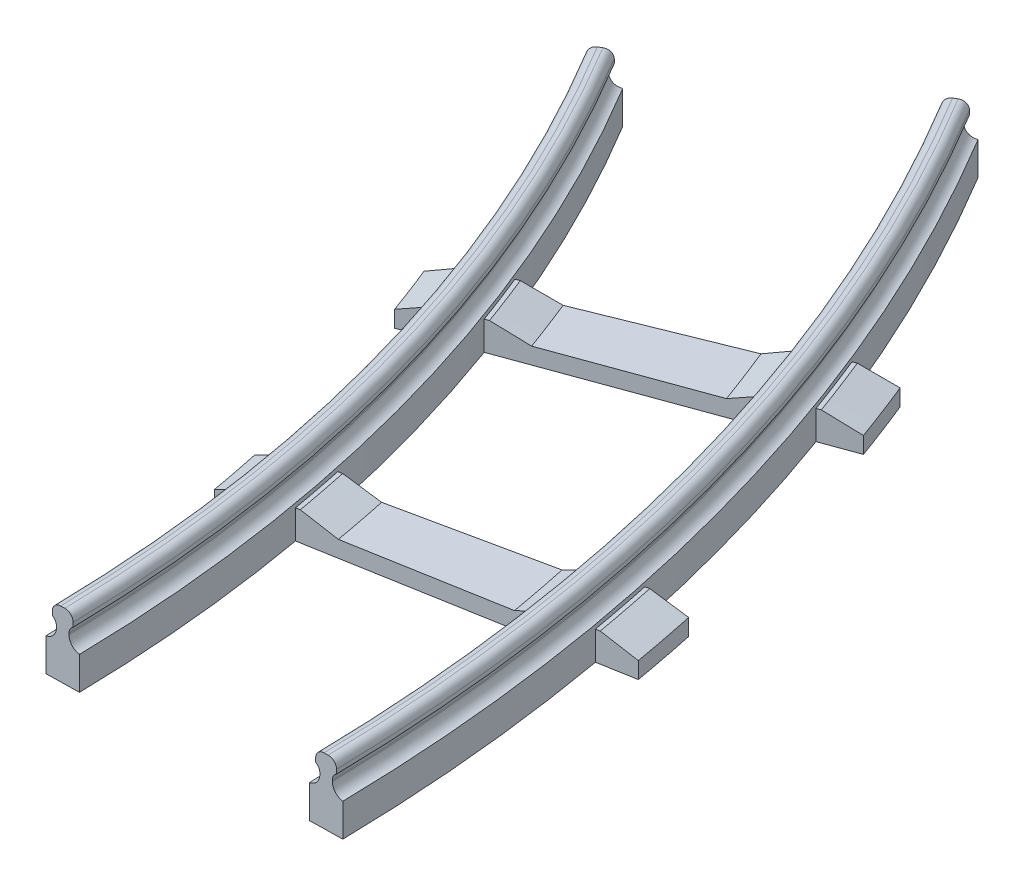
SolidWorks part; units mm, degrees
other "标注1"
sketch "草图3" plane through (-22.25, 4, -10) normal (-0.231, 0.6469, -0.7268) x (-0.9696, -0.2151, 0.1167)
other "标注2"
sketch "草图4" plane through (22.25, 8, -30) normal (0.0083, 0.0567, -0.9984) x (-0.9991, 0.0415, -0.0059)
ref_plane "前视基准面" through (0, 0, 0) normal (0, 0, 1) x (1, 0, 0)
ref_plane "上视基准面" through (0, 0, 0) normal (0, 1, 0) x (1, 0, 0)
ref_plane "右视基准面" through (0, 0, 0) normal (1, 0, 0) x (0, 0, -1)
other "Configuration Table"
sketch "草图1" plane through (0, 0, 0) normal (0, 1, 0) x (1, 0, 0)
  line L0 (-13.75, 14.5) -> (-13.75, -14.5)
  line L13 (-17.75, -14.5) -> (17.75, -14.5)
  line L21 (-17.75, -14.5) -> (-17.75, 14.5)
  line L22 (-17.75, 14.5) -> (17.75, 14.5)
  line L23 (17.75, -14.5) -> (17.75, 14.5)
  line L24 (-17.75, -14.5) -> (17.75, 14.5) construction
  line L25 (-17.75, 14.5) -> (17.75, -14.5) construction
  line L27 (13.75, 14.5) -> (13.75, -14.5)
  line L29 (-13.75, 0) -> (13.75, 0) construction
  line L32 (-22.25, 14.5) -> (22.25, 14.5)
  line L33 (-22.25, 14.5) -> (-22.25, 6.5)
  line L34 (-22.25, 6.5) -> (22.25, 6.5)
  line L35 (22.25, 14.5) -> (22.25, 6.5)
  point P0 (0, 0)
  point P15 (0, 6.5)
  dimension "D3" = 27.5
  dimension "D4" = 8
  dimension "D1" = 35.5
  dimension "D2" = 29
  dimension "D5" = 44.5
extrude "凸台-拉伸1" add sketch "草图1" along normal blind 4 contours L34 L21 L13 L0 | L34 L27 L13 L23 | L27 L34 L23 L22 | L21 L34 L0 L22 region at (-15.75, 0, -10.5) region at (-15.75, 0, 4) region at (15.75, 0, -10.5) region at (15.75, 0, 4)
extrude "凸台-拉伸2" add sketch "草图1<7>" along normal blind 3.5 contours L34 L35 L32 L33
sketch "草图1<7>" plane through (0, 0, 0) normal (0, 1, 0) x (1, 0, 0) same geometry as "草图1"
sketch "草图2" plane through (0, 0, -14.5) normal (0, 0, -1) x (-1, 0, 0)
  line L0 (18.25, 3.5) -> (22.25, 2)
  line L1 (22.25, 3.5) -> (18.25, 3.5)
  line L2 (22.25, 3.5) -> (22.25, 2)
  line L3 (22.25, 2) -> (18.25, 2) construction
  line L4 (18.25, 3.5) -> (18.25, 2) construction
  line L5 (-22.25, 2) -> (-18.25, 3.5)
  line L6 (-22.25, 3.5) -> (-18.25, 3.5)
  line L7 (-22.25, 3.5) -> (-22.25, 2)
  line L8 (-22.25, 2) -> (-18.25, 2) construction
  line L9 (-18.25, 3.5) -> (-18.25, 2) construction
  line L10 (13.75, 3.5) -> (-13.75, 3.5) construction
  line L11 (-13.25, 3.5) -> (-9.25, 3.5)
  line L12 (-13.25, 3.5) -> (-13.25, 2) construction
  line L13 (-13.25, 2) -> (-9.25, 2) construction
  line L14 (-9.25, 3.5) -> (-9.25, 2)
  line L15 (-13.75, 3.5) -> (-13.25, 3.5) construction
  line L16 (13.25, 3.5) -> (9.25, 3.5)
  line L17 (13.25, 3.5) -> (13.25, 2) construction
  line L18 (13.25, 2) -> (9.25, 2) construction
  line L19 (9.25, 3.5) -> (9.25, 2)
  line L20 (13.25, 3.5) -> (13.75, 3.5) construction
  line L21 (17.75, 3.5) -> (18.25, 3.5) construction
  line L22 (-13.25, 3.5) -> (-9.25, 2)
  line L23 (9.25, 2) -> (13.25, 3.5)
  line L24 (-9.25, 2) -> (9.25, 2)
  line L25 (-9.25, 3.5) -> (9.25, 3.5)
  line L26 (-15.75, 4) -> (-15.75, 6.5) construction
  line L27 (14.5, 8) -> (17, 8)
  line L28 (14.5, 8) -> (14.5, 6.5)
  line L29 (14.5, 6.5) -> (17, 6.5)
  line L30 (17, 8) -> (17, 6.5)
  line L31 (-17, 8) -> (-14.5, 8)
  line L32 (-17, 8) -> (-17, 6.5)
  line L33 (-17, 6.5) -> (-14.5, 6.5)
  line L34 (-14.5, 8) -> (-14.5, 6.5)
  line L35 (-13.75, 4) -> (-17.75, 4) construction
  line L36 (15.75, 6.5) -> (15.75, 4) construction
  line L37 (17.75, 4) -> (13.75, 4) construction
  line L38 (15, 6.5) -> (15, 4)
  line L39 (16.5, 6.5) -> (16.5, 4)
  line L40 (16.5, 4) -> (15.75, 4)
  line L41 (15.75, 4) -> (15, 4)
  line L42 (-16.5, 6.5) -> (-16.5, 4)
  line L43 (-16.5, 4) -> (-15.75, 4)
  line L44 (-15.75, 4) -> (-15, 4)
  line L45 (-15, 4) -> (-15, 6.5)
  line M9 (22.25, 3.5) -> (17.75, 3.5)
  line M11 (17.75, 4) -> (13.75, 4)
  line M13 (13.75, 3.5) -> (-13.75, 3.5)
  line M15 (-13.75, 4) -> (-17.75, 4)
  line M17 (-17.75, 3.5) -> (-22.25, 3.5)
  line M18 (-22.25, 3.5) -> (-22.25, 0)
  line M20 (22.25, 0) -> (22.25, 3.5)
  dimension "D1" = 4
  dimension "D2" = 1.5
  dimension "D3" = 2.5
  dimension "D4" = 1.5
  dimension "D5" = 2.5
  dimension "D6" = 1.5
extrude "切除-拉伸1" cut sketch "草图2" against normal through all contours L14 L24 L19 M13 | L19 L23 M13 | L22 L14 M13 | L5 M18 M17 | L0 M9 M20 region at (-20.9167, 3, -14.5) region at (20.9167, 3, -14.5) region at (10.5833, 3, -14.5) region at (0, 2.75, -14.5) region at (-10.5833, 3, -14.5)
extrude "凸台-拉伸4" add sketch "草图2<3>" against normal through all contours L34 L31 L32 L33 | L45 L33 L42 M15 | L30 L27 L28 L29 | L39 L29 L38 M11 region at (-15.75, 7.25, -14.5) region at (-15.75, 5.25, -14.5) region at (15.75, 7.25, -14.5) region at (15.75, 5.25, -14.5)
sketch "草图2<3>" plane through (0, 0, -14.5) normal (0, 0, -1) x (-1, 0, 0) same geometry as "草图2"
fillet "圆角1" radius 1 4 edges at (-16.5, 6.5, 0) (-15, 6.5, 0) (15, 6.5, 0) (16.5, 6.5, 0)
fillet "圆角2" radius 1.5 4 edges at (16.5, 4, 0) (15, 4, 0) (-15, 4, 0) (-16.5, 4, 0)
fillet "圆角3" radius 1 4 edges at (-17, 8, 0) (14.5, 8, 0) (17, 8, 0) (-14.5, 8, 0)
sketch "草图5" plane through (0, 0, -14.5) normal (0, 0, -1) x (-1, 0, 0)
  line L26 (17, 6.5) -> (17, 7)
  line L27 (16, 8) -> (15.5, 8)
  line L28 (14.5, 7) -> (14.5, 6.5)
  line L29 (15, 5.634) -> (15, 5.479)
  line L30 (13.75, 4) -> (13.75, 3.5)
  line L31 (13.75, 3.5) -> (13.25, 3.5)
  line L32 (13.25, 3.5) -> (9.25, 2)
  line L33 (9.25, 2) -> (-9.25, 2)
  line L34 (-9.25, 2) -> (-13.25, 3.5)
  line L35 (-13.25, 3.5) -> (-13.75, 3.5)
  line L36 (-13.75, 3.5) -> (-13.75, 4)
  line L37 (-15, 5.479) -> (-15, 5.634)
  line L38 (-14.5, 6.5) -> (-14.5, 7)
  line L39 (-15.5, 8) -> (-16, 8)
  line L40 (-17, 7) -> (-17, 6.5)
  line L41 (-16.5, 5.634) -> (-16.5, 5.479)
  line L42 (-17.75, 4) -> (-17.75, 3.5)
  line L43 (-17.75, 3.5) -> (-18.25, 3.5)
  line L44 (-18.25, 3.5) -> (-22.25, 2)
  line L45 (-22.25, 2) -> (-22.25, 0)
  line L46 (-22.25, 0) -> (22.25, 0)
  line L47 (22.25, 0) -> (22.25, 2)
  line L48 (22.25, 2) -> (18.25, 3.5)
  line L49 (18.25, 3.5) -> (17.75, 3.5)
  line L50 (17.75, 3.5) -> (17.75, 4)
  line L51 (16.5, 5.479) -> (16.5, 5.634)
  line L52 (17, 6.5) -> (17, 7)
  line L53 (16, 8) -> (15.5, 8)
  line L54 (14.5, 7) -> (14.5, 6.5)
  line L55 (15, 5.634) -> (15, 5.479)
  line L56 (13.75, 4) -> (13.75, 3.5)
  line L57 (13.75, 3.5) -> (13.25, 3.5)
  line L58 (13.25, 3.5) -> (9.25, 2)
  line L59 (9.25, 2) -> (-9.25, 2)
  line L60 (-9.25, 2) -> (-13.25, 3.5)
  line L61 (-13.25, 3.5) -> (-13.75, 3.5)
  line L62 (-13.75, 3.5) -> (-13.75, 4)
  line L63 (-15, 5.479) -> (-15, 5.634)
  line L64 (-14.5, 6.5) -> (-14.5, 7)
  line L65 (-15.5, 8) -> (-16, 8)
  line L66 (-17, 7) -> (-17, 6.5)
  line L67 (-16.5, 5.634) -> (-16.5, 5.479)
  line L68 (-17.75, 4) -> (-17.75, 3.5)
  line L69 (-17.75, 3.5) -> (-18.25, 3.5)
  line L70 (-18.25, 3.5) -> (-22.25, 2)
  line L71 (-22.25, 2) -> (-22.25, 0)
  line L72 (-22.25, 0) -> (22.25, 0)
  line L73 (22.25, 0) -> (22.25, 2)
  line L74 (22.25, 2) -> (18.25, 3.5)
  line L75 (18.25, 3.5) -> (17.75, 3.5)
  line L76 (17.75, 3.5) -> (17.75, 4)
  line L77 (16.5, 5.479) -> (16.5, 5.634)
  arc A12 (17, 7) -> (16, 8) centre (16, 7) ccw
  arc A13 (15.5, 8) -> (14.5, 7) centre (15.5, 7) ccw
  arc A14 (15, 5.634) -> (14.5, 6.5) centre (14, 5.634) ccw
  arc A15 (13.75, 4) -> (15, 5.479) centre (13.5, 5.479) ccw
  arc A16 (-15, 5.479) -> (-13.75, 4) centre (-13.5, 5.479) ccw
  arc A17 (-14.5, 6.5) -> (-15, 5.634) centre (-14, 5.634) ccw
  arc A18 (-14.5, 7) -> (-15.5, 8) centre (-15.5, 7) ccw
  arc A19 (-16, 8) -> (-17, 7) centre (-16, 7) ccw
  arc A20 (-16.5, 5.634) -> (-17, 6.5) centre (-17.5, 5.634) ccw
  arc A21 (-17.75, 4) -> (-16.5, 5.479) centre (-18, 5.479) ccw
  arc A22 (16.5, 5.479) -> (17.75, 4) centre (18, 5.479) ccw
  arc A23 (17, 6.5) -> (16.5, 5.634) centre (17.5, 5.634) ccw
  arc A24 (17, 7) -> (16, 8) centre (16, 7) ccw
  arc A25 (15.5, 8) -> (14.5, 7) centre (15.5, 7) ccw
  arc A26 (15, 5.634) -> (14.5, 6.5) centre (14, 5.634) ccw
  arc A27 (13.75, 4) -> (15, 5.479) centre (13.5, 5.479) ccw
  arc A28 (-15, 5.479) -> (-13.75, 4) centre (-13.5, 5.479) ccw
  arc A29 (-14.5, 6.5) -> (-15, 5.634) centre (-14, 5.634) ccw
  arc A30 (-14.5, 7) -> (-15.5, 8) centre (-15.5, 7) ccw
  arc A31 (-16, 8) -> (-17, 7) centre (-16, 7) ccw
  arc A32 (-16.5, 5.634) -> (-17, 6.5) centre (-17.5, 5.634) ccw
  arc A33 (-17.75, 4) -> (-16.5, 5.479) centre (-18, 5.479) ccw
  arc A34 (16.5, 5.479) -> (17.75, 4) centre (18, 5.479) ccw
  arc A35 (17, 6.5) -> (16.5, 5.634) centre (17.5, 5.634) ccw
  dimension "D1" = 0
sketch "草图7" plane through (0, 0, -14.5) normal (0, 0, -1) x (-1, 0, 0)
  line L0 (-17.75, 3.5) -> (-17.75, 0)
  line L1 (-13.75, 3.5) -> (-13.75, 0)
  line L2 (13.75, 3.5) -> (13.75, 0)
  line L3 (17.75, 3.5) -> (17.75, 0)
  line L4 (13.75, 0) -> (17.75, 0)
  line L26 (17, 6.5) -> (17, 7)
  line L27 (16, 8) -> (15.5, 8)
  line L28 (14.5, 7) -> (14.5, 6.5)
  line L29 (15, 5.634) -> (15, 5.479)
  line L30 (13.75, 4) -> (13.75, 3.5)
  line L31 (13.75, 3.5) -> (13.25, 3.5)
  line L32 (13.25, 3.5) -> (9.25, 2)
  line L33 (9.25, 2) -> (-9.25, 2)
  line L34 (-9.25, 2) -> (-13.25, 3.5)
  line L35 (-13.25, 3.5) -> (-13.75, 3.5)
  line L36 (-13.75, 3.5) -> (-13.75, 4)
  line L37 (-15, 5.479) -> (-15, 5.634)
  line L38 (-14.5, 6.5) -> (-14.5, 7)
  line L39 (-15.5, 8) -> (-16, 8)
  line L40 (-17, 7) -> (-17, 6.5)
  line L41 (-16.5, 5.634) -> (-16.5, 5.479)
  line L42 (-17.75, 4) -> (-17.75, 3.5)
  line L43 (-17.75, 3.5) -> (-18.25, 3.5)
  line L44 (-18.25, 3.5) -> (-22.25, 2)
  line L45 (-22.25, 2) -> (-22.25, 0)
  line L46 (-22.25, 0) -> (22.25, 0)
  line L47 (22.25, 0) -> (22.25, 2)
  line L48 (22.25, 2) -> (18.25, 3.5)
  line L49 (18.25, 3.5) -> (17.75, 3.5)
  line L50 (17.75, 3.5) -> (17.75, 4)
  line L51 (16.5, 5.479) -> (16.5, 5.634)
  line L52 (17, 6.5) -> (17, 7)
  line L53 (16, 8) -> (15.5, 8)
  line L54 (14.5, 7) -> (14.5, 6.5)
  line L55 (15, 5.634) -> (15, 5.479)
  line L56 (13.75, 4) -> (13.75, 3.5)
  line L62 (-13.75, 3.5) -> (-13.75, 4)
  line L63 (-15, 5.479) -> (-15, 5.634)
  line L64 (-14.5, 6.5) -> (-14.5, 7)
  line L65 (-15.5, 8) -> (-16, 8)
  line L66 (-17, 7) -> (-17, 6.5)
  line L67 (-16.5, 5.634) -> (-16.5, 5.479)
  line L68 (-17.75, 4) -> (-17.75, 3.5)
  line L72 (-17.75, 0) -> (-13.75, 0)
  line L76 (17.75, 3.5) -> (17.75, 4)
  line L77 (16.5, 5.479) -> (16.5, 5.634)
  arc A12 (17, 7) -> (16, 8) centre (16, 7) ccw
  arc A13 (15.5, 8) -> (14.5, 7) centre (15.5, 7) ccw
  arc A14 (15, 5.634) -> (14.5, 6.5) centre (14, 5.634) ccw
  arc A15 (13.75, 4) -> (15, 5.479) centre (13.5, 5.479) ccw
  arc A16 (-15, 5.479) -> (-13.75, 4) centre (-13.5, 5.479) ccw
  arc A17 (-14.5, 6.5) -> (-15, 5.634) centre (-14, 5.634) ccw
  arc A18 (-14.5, 7) -> (-15.5, 8) centre (-15.5, 7) ccw
  arc A19 (-16, 8) -> (-17, 7) centre (-16, 7) ccw
  arc A20 (-16.5, 5.634) -> (-17, 6.5) centre (-17.5, 5.634) ccw
  arc A21 (-17.75, 4) -> (-16.5, 5.479) centre (-18, 5.479) ccw
  arc A22 (16.5, 5.479) -> (17.75, 4) centre (18, 5.479) ccw
  arc A23 (17, 6.5) -> (16.5, 5.634) centre (17.5, 5.634) ccw
  arc A24 (17, 7) -> (16, 8) centre (16, 7) ccw
  arc A25 (15.5, 8) -> (14.5, 7) centre (15.5, 7) ccw
  arc A26 (15, 5.634) -> (14.5, 6.5) centre (14, 5.634) ccw
  arc A27 (13.75, 4) -> (15, 5.479) centre (13.5, 5.479) ccw
  arc A28 (-15, 5.479) -> (-13.75, 4) centre (-13.5, 5.479) ccw
  arc A29 (-14.5, 6.5) -> (-15, 5.634) centre (-14, 5.634) ccw
  arc A30 (-14.5, 7) -> (-15.5, 8) centre (-15.5, 7) ccw
  arc A31 (-16, 8) -> (-17, 7) centre (-16, 7) ccw
  arc A32 (-16.5, 5.634) -> (-17, 6.5) centre (-17.5, 5.634) ccw
  arc A33 (-17.75, 4) -> (-16.5, 5.479) centre (-18, 5.479) ccw
  arc A34 (16.5, 5.479) -> (17.75, 4) centre (18, 5.479) ccw
  arc A35 (17, 6.5) -> (16.5, 5.634) centre (17.5, 5.634) ccw
  dimension "D1" = 0
sketch "草图6" plane through (0, 0, -14.5) normal (0, 0, -1) x (-1, 0, 0)
  line L0 (0, 0) -> (200, 0) construction
  line L1 (200, 10) -> (200, -10)
  dimension "D1" = 200
  dimension "D2" = 20
revolve "旋转2" add sketch "草图7" angle 32 about L1 reverse direction yes
extrude "切除-拉伸5" cut sketch "草图5<2>" against normal through all
sketch "草图5<2>" plane through (0, 0, -14.5) normal (0, 0, -1) x (-1, 0, 0) same geometry as "草图5"
revolve "旋转1" add sketch "草图5" angle 2 about L1 reverse direction yes
pattern_circular "阵列(圆周)1" count 4 every 10 about axis through (-200, 10, -14.5) along (0, -1, 0) of "旋转1" reverse direction yes
sketch "草图8" plane through (0, 0, -14.5) normal (0, 0, 1) x (1, 0, 0)
  line L78 (-22.25, 2) -> (-22.25, 0)
  line L79 (-22.25, 0) -> (22.25, 0)
  line L80 (22.25, 0) -> (22.25, 2)
  line L81 (22.25, 2) -> (18.25, 3.5)
  line L82 (18.25, 3.5) -> (17.75, 3.5)
  line L83 (17.75, 3.5) -> (17.75, 4)
  line L84 (16.5, 5.479) -> (16.5, 5.634)
  line L85 (17, 6.5) -> (17, 7)
  line L86 (16, 8) -> (15.5, 8)
  line L87 (14.5, 7) -> (14.5, 6.5)
  line L88 (15, 5.634) -> (15, 5.479)
  line L89 (13.75, 4) -> (13.75, 3.5)
  line L90 (13.75, 3.5) -> (13.25, 3.5)
  line L91 (13.25, 3.5) -> (9.25, 2)
  line L92 (9.25, 2) -> (-9.25, 2)
  line L93 (-9.25, 2) -> (-13.25, 3.5)
  line L94 (-13.25, 3.5) -> (-13.75, 3.5)
  line L95 (-13.75, 3.5) -> (-13.75, 4)
  line L96 (-15, 5.479) -> (-15, 5.634)
  line L97 (-14.5, 6.5) -> (-14.5, 7)
  line L98 (-15.5, 8) -> (-16, 8)
  line L99 (-17, 7) -> (-17, 6.5)
  line L100 (-16.5, 5.634) -> (-16.5, 5.479)
  line L101 (-17.75, 4) -> (-17.75, 3.5)
  line L102 (-17.75, 3.5) -> (-18.25, 3.5)
  line L103 (-18.25, 3.5) -> (-22.25, 2)
  line L104 (-22.25, 2) -> (-22.25, 0)
  line L105 (-22.25, 0) -> (22.25, 0)
  line L106 (22.25, 0) -> (22.25, 2)
  line L107 (22.25, 2) -> (18.25, 3.5)
  line L108 (18.25, 3.5) -> (17.75, 3.5)
  line L109 (17.75, 3.5) -> (17.75, 4)
  line L110 (16.5, 5.479) -> (16.5, 5.634)
  line L111 (17, 6.5) -> (17, 7)
  line L112 (16, 8) -> (15.5, 8)
  line L113 (14.5, 7) -> (14.5, 6.5)
  line L114 (15, 5.634) -> (15, 5.479)
  line L115 (13.75, 4) -> (13.75, 3.5)
  line L116 (13.75, 3.5) -> (13.25, 3.5)
  line L117 (13.25, 3.5) -> (9.25, 2)
  line L118 (9.25, 2) -> (-9.25, 2)
  line L119 (-9.25, 2) -> (-13.25, 3.5)
  line L120 (-13.25, 3.5) -> (-13.75, 3.5)
  line L121 (-13.75, 3.5) -> (-13.75, 4)
  line L122 (-15, 5.479) -> (-15, 5.634)
  line L123 (-14.5, 6.5) -> (-14.5, 7)
  line L124 (-15.5, 8) -> (-16, 8)
  line L125 (-17, 7) -> (-17, 6.5)
  line L126 (-16.5, 5.634) -> (-16.5, 5.479)
  line L127 (-17.75, 4) -> (-17.75, 3.5)
  line L128 (-17.75, 3.5) -> (-18.25, 3.5)
  line L129 (-18.25, 3.5) -> (-22.25, 2)
  arc A36 (16.5, 5.479) -> (17.75, 4) centre (18, 5.479) ccw
  arc A37 (17, 6.5) -> (16.5, 5.634) centre (17.5, 5.634) ccw
  arc A38 (17, 7) -> (16, 8) centre (16, 7) ccw
  arc A39 (15.5, 8) -> (14.5, 7) centre (15.5, 7) ccw
  arc A40 (15, 5.634) -> (14.5, 6.5) centre (14, 5.634) ccw
  arc A41 (13.75, 4) -> (15, 5.479) centre (13.5, 5.479) ccw
  arc A42 (-15, 5.479) -> (-13.75, 4) centre (-13.5, 5.479) ccw
  arc A43 (-14.5, 6.5) -> (-15, 5.634) centre (-14, 5.634) ccw
  arc A44 (-14.5, 7) -> (-15.5, 8) centre (-15.5, 7) ccw
  arc A45 (-16, 8) -> (-17, 7) centre (-16, 7) ccw
  arc A46 (-16.5, 5.634) -> (-17, 6.5) centre (-17.5, 5.634) ccw
  arc A47 (-17.75, 4) -> (-16.5, 5.479) centre (-18, 5.479) ccw
  arc A48 (16.5, 5.479) -> (17.75, 4) centre (18, 5.479) ccw
  arc A49 (17, 6.5) -> (16.5, 5.634) centre (17.5, 5.634) ccw
  arc A50 (17, 7) -> (16, 8) centre (16, 7) ccw
  arc A51 (15.5, 8) -> (14.5, 7) centre (15.5, 7) ccw
  arc A52 (15, 5.634) -> (14.5, 6.5) centre (14, 5.634) ccw
  arc A53 (13.75, 4) -> (15, 5.479) centre (13.5, 5.479) ccw
  arc A54 (-15, 5.479) -> (-13.75, 4) centre (-13.5, 5.479) ccw
  arc A55 (-14.5, 6.5) -> (-15, 5.634) centre (-14, 5.634) ccw
  arc A56 (-14.5, 7) -> (-15.5, 8) centre (-15.5, 7) ccw
  arc A57 (-16, 8) -> (-17, 7) centre (-16, 7) ccw
  arc A58 (-16.5, 5.634) -> (-17, 6.5) centre (-17.5, 5.634) ccw
  arc A59 (-17.75, 4) -> (-16.5, 5.479) centre (-18, 5.479) ccw
  dimension "D1" = 0
revolve "切除-旋转1" cut sketch "草图8" angle 1 about L1 reverse direction yes
sketch "草图9" plane through (-62.6791, 0, -100.3076) normal (-0.5299, 0, -0.848) x (-0.848, 0, 0.5299)
  line L26 (-60.3242, 0) -> (-15.8242, 0)
  line L27 (-15.8242, 0) -> (-15.8242, 2)
  line L28 (-15.8242, 0) -> (-15.8242, 2)
  line L29 (-15.8242, 2) -> (-19.8242, 3.5)
  line L30 (-20.3242, 3.5) -> (-20.3242, 4)
  line L31 (-21.5742, 5.479) -> (-21.5742, 5.634)
  line L32 (-21.0742, 6.5) -> (-21.0742, 7)
  line L33 (-22.0742, 8) -> (-22.5742, 8)
  line L34 (-23.5742, 7) -> (-23.5742, 6.5)
  line L35 (-23.0742, 5.634) -> (-23.0742, 5.479)
  line L36 (-24.3242, 4) -> (-24.3242, 3.5)
  line L37 (-15.8242, 2) -> (-19.8242, 3.5)
  line L38 (-19.8242, 3.5) -> (-20.3242, 3.5)
  line L39 (-19.8242, 3.5) -> (-20.3242, 3.5)
  line L40 (-24.3242, 3.5) -> (-24.8242, 3.5)
  line L41 (-24.3242, 3.5) -> (-24.8242, 3.5)
  line L42 (-51.8242, 3.5) -> (-51.8242, 4)
  line L43 (-53.0742, 5.479) -> (-53.0742, 5.634)
  line L44 (-52.5742, 6.5) -> (-52.5742, 7)
  line L45 (-53.5742, 8) -> (-54.0742, 8)
  line L46 (-55.0742, 7) -> (-55.0742, 6.5)
  line L47 (-54.5742, 5.634) -> (-54.5742, 5.479)
  line L48 (-55.8242, 4) -> (-55.8242, 3.5)
  line L49 (-24.8242, 3.5) -> (-28.8242, 2)
  line L50 (-24.8242, 3.5) -> (-28.8242, 2)
  line L51 (-28.8242, 2) -> (-47.3242, 2)
  line L52 (-60.3242, 0) -> (-15.8242, 0)
  line L56 (-20.3242, 3.5) -> (-20.3242, 4)
  line L57 (-21.5742, 5.479) -> (-21.5742, 5.634)
  line L58 (-21.0742, 6.5) -> (-21.0742, 7)
  line L59 (-22.0742, 8) -> (-22.5742, 8)
  line L60 (-23.5742, 7) -> (-23.5742, 6.5)
  line L61 (-23.0742, 5.634) -> (-23.0742, 5.479)
  line L62 (-24.3242, 4) -> (-24.3242, 3.5)
  line L68 (-51.8242, 3.5) -> (-51.8242, 4)
  line L69 (-53.0742, 5.479) -> (-53.0742, 5.634)
  line L70 (-52.5742, 6.5) -> (-52.5742, 7)
  line L71 (-53.5742, 8) -> (-54.0742, 8)
  line L72 (-55.0742, 7) -> (-55.0742, 6.5)
  line L73 (-54.5742, 5.634) -> (-54.5742, 5.479)
  line L74 (-55.8242, 4) -> (-55.8242, 3.5)
  line L78 (-28.8242, 2) -> (-47.3242, 2)
  line L79 (-47.3242, 2) -> (-51.3242, 3.5)
  line L80 (-47.3242, 2) -> (-51.3242, 3.5)
  line L81 (-51.3242, 3.5) -> (-51.8242, 3.5)
  line L82 (-51.3242, 3.5) -> (-51.8242, 3.5)
  line L83 (-55.8242, 3.5) -> (-56.3242, 3.5)
  line L84 (-55.8242, 3.5) -> (-56.3242, 3.5)
  line L85 (-56.3242, 3.5) -> (-60.3242, 2)
  line L86 (-56.3242, 3.5) -> (-60.3242, 2)
  line L87 (-60.3242, 2) -> (-60.3242, 0)
  line L88 (-60.3242, 2) -> (-60.3242, 0)
  arc A12 (-21.5742, 5.479) -> (-20.3242, 4) centre (-20.0742, 5.479) ccw
  arc A13 (-21.0742, 6.5) -> (-21.5742, 5.634) centre (-20.5742, 5.634) ccw
  arc A14 (-21.0742, 7) -> (-22.0742, 8) centre (-22.0742, 7) ccw
  arc A15 (-22.5742, 8) -> (-23.5742, 7) centre (-22.5742, 7) ccw
  arc A16 (-23.0742, 5.634) -> (-23.5742, 6.5) centre (-24.0742, 5.634) ccw
  arc A17 (-24.3242, 4) -> (-23.0742, 5.479) centre (-24.5742, 5.479) ccw
  arc A18 (-53.0742, 5.479) -> (-51.8242, 4) centre (-51.5742, 5.479) ccw
  arc A19 (-52.5742, 6.5) -> (-53.0742, 5.634) centre (-52.0742, 5.634) ccw
  arc A20 (-52.5742, 7) -> (-53.5742, 8) centre (-53.5742, 7) ccw
  arc A21 (-54.0742, 8) -> (-55.0742, 7) centre (-54.0742, 7) ccw
  arc A22 (-54.5742, 5.634) -> (-55.0742, 6.5) centre (-55.5742, 5.634) ccw
  arc A23 (-55.8242, 4) -> (-54.5742, 5.479) centre (-56.0742, 5.479) ccw
  arc A24 (-21.5742, 5.479) -> (-20.3242, 4) centre (-20.0742, 5.479) ccw
  arc A25 (-21.0742, 6.5) -> (-21.5742, 5.634) centre (-20.5742, 5.634) ccw
  arc A26 (-21.0742, 7) -> (-22.0742, 8) centre (-22.0742, 7) ccw
  arc A27 (-22.5742, 8) -> (-23.5742, 7) centre (-22.5742, 7) ccw
  arc A28 (-23.0742, 5.634) -> (-23.5742, 6.5) centre (-24.0742, 5.634) ccw
  arc A29 (-24.3242, 4) -> (-23.0742, 5.479) centre (-24.5742, 5.479) ccw
  arc A30 (-53.0742, 5.479) -> (-51.8242, 4) centre (-51.5742, 5.479) ccw
  arc A31 (-52.5742, 6.5) -> (-53.0742, 5.634) centre (-52.0742, 5.634) ccw
  arc A32 (-52.5742, 7) -> (-53.5742, 8) centre (-53.5742, 7) ccw
  arc A33 (-54.0742, 8) -> (-55.0742, 7) centre (-54.0742, 7) ccw
  arc A34 (-54.5742, 5.634) -> (-55.0742, 6.5) centre (-55.5742, 5.634) ccw
  arc A35 (-55.8242, 4) -> (-54.5742, 5.479) centre (-56.0742, 5.479) ccw
  dimension "D1" = 0
revolve "切除-旋转2" cut sketch "草图9" angle 1 about L1
sketch "草图10" plane through (-0.3139, 0, -17.9855) normal (0.0175, 0, 0.9998) x (0.9998, 0, -0.0175)
  line L0 (-17.4665, 3.5) -> (-17.4665, 0)
  line L1 (-13.4665, 3.5) -> (-13.4665, 0)
  line L2 (14.0335, 3.5) -> (14.0335, 0)
  line L3 (18.0335, 3.5) -> (18.0335, 0)
  line L4 (-13.4665, 0) -> (14.0335, 0)
  line L5 (18.0335, 0) -> (22.5335, 0)
  line L26 (-17.9665, 3.5) -> (-21.9665, 2)
  line L27 (-21.9665, 2) -> (-21.9665, 0)
  line L28 (-21.9665, 0) -> (22.5335, 0)
  line L29 (22.5335, 0) -> (22.5335, 2)
  line L30 (22.5335, 2) -> (18.5335, 3.5)
  line L31 (18.5335, 3.5) -> (18.0335, 3.5)
  line L32 (18.0335, 3.5) -> (18.0335, 4)
  line L33 (16.7835, 5.479) -> (16.7835, 5.634)
  line L34 (17.2835, 6.5) -> (17.2835, 7)
  line L35 (16.2835, 8) -> (15.7835, 8)
  line L36 (14.7835, 7) -> (14.7835, 6.5)
  line L37 (15.2835, 5.634) -> (15.2835, 5.479)
  line L38 (14.0335, 4) -> (14.0335, 3.5)
  line L39 (14.0335, 3.5) -> (13.5335, 3.5)
  line L40 (13.5335, 3.5) -> (9.5335, 2)
  line L41 (9.5335, 2) -> (-8.9665, 2)
  line L42 (-8.9665, 2) -> (-12.9665, 3.5)
  line L43 (-12.9665, 3.5) -> (-13.4665, 3.5)
  line L44 (-13.4665, 3.5) -> (-13.4665, 4)
  line L45 (-14.7165, 5.479) -> (-14.7165, 5.634)
  line L46 (-14.2165, 6.5) -> (-14.2165, 7)
  line L47 (-15.2165, 8) -> (-15.7165, 8)
  line L48 (-16.7165, 7) -> (-16.7165, 6.5)
  line L49 (-16.2165, 5.634) -> (-16.2165, 5.479)
  line L50 (-17.4665, 4) -> (-17.4665, 3.5)
  line L51 (-17.4665, 3.5) -> (-17.9665, 3.5)
  line L52 (-17.9665, 3.5) -> (-21.9665, 2)
  line L53 (-21.9665, 2) -> (-21.9665, 0)
  line L54 (-21.9665, 0) -> (-17.4665, 0)
  line L55 (22.5335, 0) -> (22.5335, 2)
  line L56 (22.5335, 2) -> (18.5335, 3.5)
  line L57 (18.5335, 3.5) -> (18.0335, 3.5)
  line L65 (14.0335, 3.5) -> (13.5335, 3.5)
  line L66 (13.5335, 3.5) -> (9.5335, 2)
  line L67 (9.5335, 2) -> (-8.9665, 2)
  line L68 (-8.9665, 2) -> (-12.9665, 3.5)
  line L69 (-12.9665, 3.5) -> (-13.4665, 3.5)
  line L77 (-17.4665, 3.5) -> (-17.9665, 3.5)
  arc A12 (16.7835, 5.479) -> (18.0335, 4) centre (18.2835, 5.479) ccw
  arc A13 (17.2835, 6.5) -> (16.7835, 5.634) centre (17.7835, 5.634) ccw
  arc A14 (17.2835, 7) -> (16.2835, 8) centre (16.2835, 7) ccw
  arc A15 (15.7835, 8) -> (14.7835, 7) centre (15.7835, 7) ccw
  arc A16 (15.2835, 5.634) -> (14.7835, 6.5) centre (14.2835, 5.634) ccw
  arc A17 (14.0335, 4) -> (15.2835, 5.479) centre (13.7835, 5.479) ccw
  arc A18 (-14.7165, 5.479) -> (-13.4665, 4) centre (-13.2165, 5.479) ccw
  arc A19 (-14.2165, 6.5) -> (-14.7165, 5.634) centre (-13.7165, 5.634) ccw
  arc A20 (-14.2165, 7) -> (-15.2165, 8) centre (-15.2165, 7) ccw
  arc A21 (-15.7165, 8) -> (-16.7165, 7) centre (-15.7165, 7) ccw
  arc A22 (-16.2165, 5.634) -> (-16.7165, 6.5) centre (-17.2165, 5.634) ccw
  arc A23 (-17.4665, 4) -> (-16.2165, 5.479) centre (-17.7165, 5.479) ccw
  dimension "D1" = 0
revolve "切除-旋转3" cut sketch "草图10" angle 1 about L1 reverse direction yes
sketch "草图11" plane through (-59.4542, 0, -98.9484) normal (-0.515, 0, -0.8572) x (-0.8572, 0, 0.515)
  line L0 (-53.7846, 3.5) -> (-53.7846, 0)
  line L1 (-49.7846, 3.5) -> (-49.7846, 0)
  line L2 (-22.2846, 3.5) -> (-22.2846, 0)
  line L3 (-18.2846, 3.5) -> (-18.2846, 0)
  line L4 (-49.7846, 0) -> (-22.2846, 0)
  line L5 (-18.2846, 0) -> (-13.7846, 0)
  line L26 (-58.2846, 2) -> (-58.2846, 0)
  line L27 (-58.2846, 0) -> (-13.7846, 0)
  line L28 (-58.2846, 2) -> (-58.2846, 0)
  line L29 (-13.7846, 0) -> (-13.7846, 2)
  line L30 (-13.7846, 0) -> (-13.7846, 2)
  line L31 (-18.2846, 3.5) -> (-18.2846, 4)
  line L32 (-19.5346, 5.479) -> (-19.5346, 5.634)
  line L33 (-19.0346, 6.5) -> (-19.0346, 7)
  line L34 (-20.0346, 8) -> (-20.5346, 8)
  line L35 (-21.5346, 7) -> (-21.5346, 6.5)
  line L36 (-21.0346, 5.634) -> (-21.0346, 5.479)
  line L37 (-22.2846, 4) -> (-22.2846, 3.5)
  line L38 (-13.7846, 2) -> (-17.7846, 3.5)
  line L39 (-13.7846, 2) -> (-17.7846, 3.5)
  line L40 (-17.7846, 3.5) -> (-18.2846, 3.5)
  line L41 (-17.7846, 3.5) -> (-18.2846, 3.5)
  line L42 (-22.2846, 3.5) -> (-22.7846, 3.5)
  line L43 (-49.7846, 3.5) -> (-49.7846, 4)
  line L44 (-51.0346, 5.479) -> (-51.0346, 5.634)
  line L45 (-50.5346, 6.5) -> (-50.5346, 7)
  line L46 (-51.5346, 8) -> (-52.0346, 8)
  line L47 (-53.0346, 7) -> (-53.0346, 6.5)
  line L48 (-52.5346, 5.634) -> (-52.5346, 5.479)
  line L49 (-53.7846, 4) -> (-53.7846, 3.5)
  line L50 (-22.2846, 3.5) -> (-22.7846, 3.5)
  line L51 (-22.7846, 3.5) -> (-26.7846, 2)
  line L53 (-58.2846, 0) -> (-53.7846, 0)
  line L84 (-22.7846, 3.5) -> (-26.7846, 2)
  line L85 (-26.7846, 2) -> (-45.2846, 2)
  line L86 (-26.7846, 2) -> (-45.2846, 2)
  line L87 (-45.2846, 2) -> (-49.2846, 3.5)
  line L88 (-45.2846, 2) -> (-49.2846, 3.5)
  line L89 (-49.2846, 3.5) -> (-49.7846, 3.5)
  line L90 (-49.2846, 3.5) -> (-49.7846, 3.5)
  line L91 (-53.7846, 3.5) -> (-54.2846, 3.5)
  line L92 (-53.7846, 3.5) -> (-54.2846, 3.5)
  line L93 (-54.2846, 3.5) -> (-58.2846, 2)
  line L94 (-54.2846, 3.5) -> (-58.2846, 2)
  arc A12 (-19.5346, 5.479) -> (-18.2846, 4) centre (-18.0346, 5.479) ccw
  arc A13 (-19.0346, 6.5) -> (-19.5346, 5.634) centre (-18.5346, 5.634) ccw
  arc A14 (-19.0346, 7) -> (-20.0346, 8) centre (-20.0346, 7) ccw
  arc A15 (-20.5346, 8) -> (-21.5346, 7) centre (-20.5346, 7) ccw
  arc A16 (-21.0346, 5.634) -> (-21.5346, 6.5) centre (-22.0346, 5.634) ccw
  arc A17 (-22.2846, 4) -> (-21.0346, 5.479) centre (-22.5346, 5.479) ccw
  arc A18 (-51.0346, 5.479) -> (-49.7846, 4) centre (-49.5346, 5.479) ccw
  arc A19 (-50.5346, 6.5) -> (-51.0346, 5.634) centre (-50.0346, 5.634) ccw
  arc A20 (-50.5346, 7) -> (-51.5346, 8) centre (-51.5346, 7) ccw
  arc A21 (-52.0346, 8) -> (-53.0346, 7) centre (-52.0346, 7) ccw
  arc A22 (-52.5346, 5.634) -> (-53.0346, 6.5) centre (-53.5346, 5.634) ccw
  arc A23 (-53.7846, 4) -> (-52.5346, 5.479) centre (-54.0346, 5.479) ccw
  point P0 (-52.197, 0)
  dimension "D1" = 0
revolve "切除-旋转4" cut sketch "草图11" angle 1 about L1
